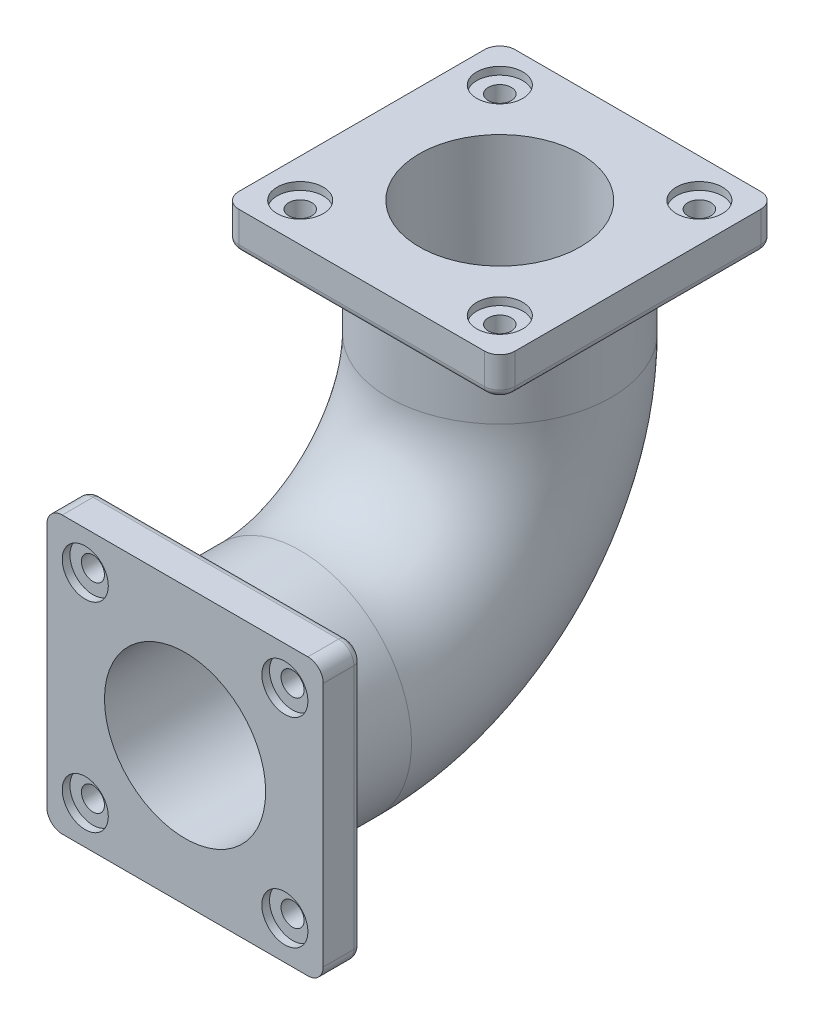
SolidWorks part; units mm, degrees
ref_plane "Ön Düzlem" through (0, 0, 0) normal (0, 0, 1) x (1, 0, 0)
ref_plane "Üst Düzlem" through (0, 0, 0) normal (0, 1, 0) x (1, 0, 0)
ref_plane "Sağ Düzlem" through (0, 0, 0) normal (1, 0, 0) x (0, 0, -1)
sketch "Çizim3" plane through (0, 0, 0) normal (0, 0, 1) x (1, 0, 0)
  line L0 (0, 144.9198) -> (0, -201.6136) construction
  line L1 (307.6758, 0) -> (-266.9072, 0) construction
  line L3 (-160, -180) -> (160, -180)
  line L4 (-180, -160) -> (-180, 160)
  line L5 (-160, 180) -> (160, 180)
  line L6 (180, -160) -> (180, 160)
  line L7 (-180, -180) -> (180, 180) construction
  line L8 (-180, 180) -> (180, -180) construction
  circle A0 centre (0, 0) radius 105
  circle A1 centre (-130, 130) radius 15
  circle A2 centre (130, 130) radius 15
  circle A3 centre (-130, -130) radius 15
  circle A4 centre (130, -130) radius 15
  arc A5 (-160, -180) -> (-180, -160) centre (-160, -160) cw
  arc A6 (160, -180) -> (180, -160) centre (160, -160) ccw
  arc A7 (160, 180) -> (180, 160) centre (160, 160) cw
  arc A8 (-180, 160) -> (-160, 180) centre (-160, 160) cw
  dimension "D1" = 210
  dimension "D2" = 30
  dimension "D3" = 130
  dimension "D7" = 20
  dimension "D4" = 130
  dimension "D5" = 360
  dimension "D6" = 360
extrude "Yükseklik-Ekstrüzyon1" add sketch "Çizim3" against normal blind 50
sketch "Çizim4" plane through (0, 0, 0) normal (0, 0, 1) x (1, 0, 0)
  circle A0 centre (-130, 130) radius 30
  circle A1 centre (130, 130) radius 30
  circle A2 centre (130, -130) radius 30
  circle A3 centre (-130, -130) radius 30
  dimension "D1" = 60
extrude "Kes-Ekstrüzyon1" cut sketch "Çizim4" against normal blind 10
sketch "Çizim5" plane through (0, 0, -50) normal (0, 0, -1) x (-1, 0, 0)
  circle A0 centre (0, 0) radius 145
  dimension "D1" = 290
extrude "Ekstrüzyon-İnce1" add sketch "Çizim5" along normal blind 100 thin thin type one direction reverse wall 40
sketch "Çizim95" plane through (0, 0, -150) normal (0, 0, -1) x (-1, 0, 0)
  circle A0 centre (0, 0) radius 105 construction
  circle A1 centre (0, 0) radius 145 construction
  circle A2 centre (0, 0) radius 105
  circle A3 centre (0, 0) radius 145
sketch "Çizim6" plane through (0, 0, 0) normal (1, 0, 0) x (0, 0, -1)
  line L1 (150, -145) -> (150, 145) construction
  arc A0 (150, 0) -> (410, 260) centre (150, 260) ccw
  dimension "D1" = 260
  dimension "D2" = 260
sweep "Süpür1" add profiles "Çizim95" path "Çizim6"
ref_plane "Düzlem1" through (0, 0, -150) normal (0, 0, 1) x (1, 0, 0)
ref_plane "Düzlem2" through (0, 205, -205) normal (0, 0.7071, -0.7071) x (-1, 0, 0)
mirror "Aynalama1" about plane through (0, 205, -205) normal (0, 0.7071, -0.7071) of "Ekstrüzyon-İnce1"
mirror "Aynalama2" about plane through (0, 205, -205) normal (0, 0.7071, -0.7071) of "Kes-Ekstrüzyon1", "Yükseklik-Ekstrüzyon1"
fillet "Radyus1" radius 10 8 edges at (174.1421, 360, -584.1421) (0, 360, -590) (-174.1421, 360, -584.1421) (-180, 360, -410) (-174.1421, 360, -235.8579) (0, 360, -230) (174.1421, 360, -235.8579) (180, 360, -410)
fillet "Radyus2" radius 10 8 edges at (174.1421, -174.1421, -50) (0, -180, -50) (-174.1421, -174.1421, -50) (-180, 0, -50) (-174.1421, 174.1421, -50) (0, 180, -50) (174.1421, 174.1421, -50) (180, 0, -50)
